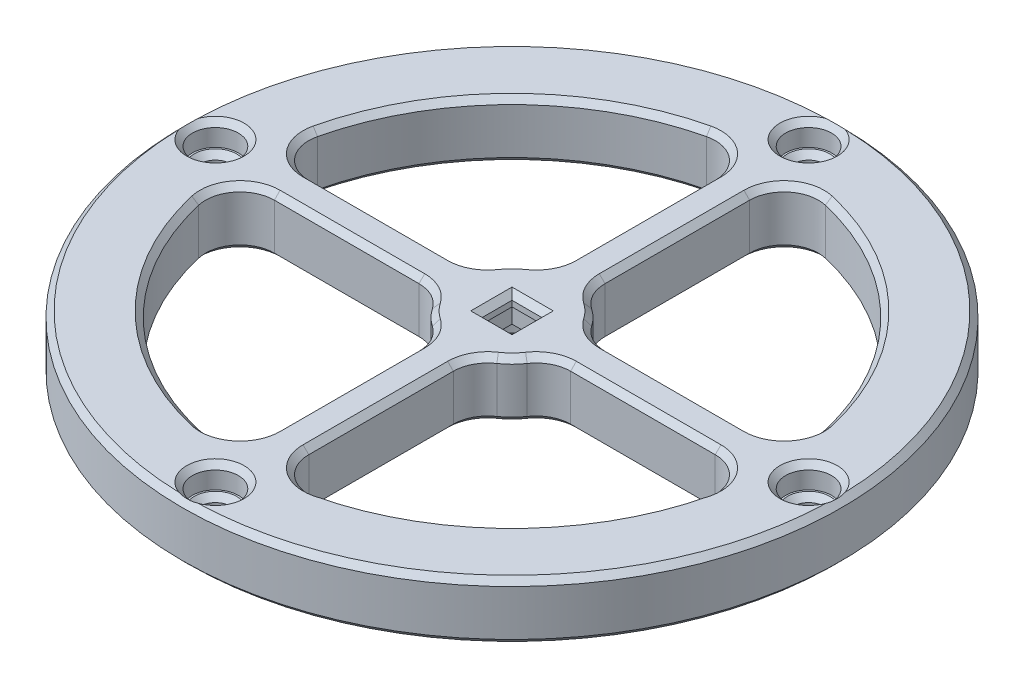
SolidWorks part; units mm, degrees
note: The reader was unsure of these and kept them because the rebuilt part matched: shared geometry of "Sketch1<4>", "Sketch1<5>".
ref_plane "Front Plane" through (0, 0, 0) normal (0, 0, 1) x (1, 0, 0)
ref_plane "Top Plane" through (0, 0, 0) normal (0, 1, 0) x (1, 0, 0)
ref_plane "Right Plane" through (0, 0, 0) normal (1, 0, 0) x (0, 0, -1)
sketch "Sketch1" plane through (0, 0, 0) normal (0, 1, 0) x (1, 0, 0)
  line L0 (0, 0) -> (0, 32.8612) construction
  line L1 (-1.651, -1.651) -> (1.651, -1.651)
  line L2 (-1.651, -1.651) -> (-1.651, 1.651)
  line L3 (-1.651, 1.651) -> (1.651, 1.651)
  line L4 (1.651, -1.651) -> (1.651, 1.651)
  line L5 (-1.651, -1.651) -> (1.651, 1.651) construction
  line L6 (-1.651, 1.651) -> (1.651, -1.651) construction
  line L7 (1.905, 0) -> (1.905, 32.8612)
  line L8 (-1.905, 0) -> (-1.905, 32.8612)
  line L9 (0, 1.905) -> (32.8612, 1.905)
  line L10 (0, -1.905) -> (32.8612, -1.905)
  line L11 (0, 0) -> (32.8612, 0) construction
  line L12 (1.905, 0) -> (1.905, -32.8612)
  line L13 (-1.905, 0) -> (-1.905, -32.8612)
  line L14 (0, 0) -> (0, -32.8612) construction
  line L15 (0, -1.905) -> (-32.8612, -1.905)
  line L16 (0, 1.905) -> (-32.8612, 1.905)
  line L17 (0, 0) -> (-32.8612, 0) construction
  line L18 (0, 0) -> (28.4587, 16.4306) construction
  line L19 (-3.175, -3.175) -> (3.175, -3.175)
  line L20 (-3.175, -3.175) -> (-3.175, 3.175)
  line L21 (-3.175, 3.175) -> (3.175, 3.175)
  line L22 (3.175, -3.175) -> (3.175, 3.175)
  line L23 (-3.175, -3.175) -> (3.175, 3.175) construction
  line L24 (-3.175, 3.175) -> (3.175, -3.175) construction
  line L25 (0, 0) -> (28.4587, -16.4306) construction
  line L26 (0, 0) -> (0, -32.8612) construction
  line L27 (0, 0) -> (-28.4587, -16.4306) construction
  line L28 (0, 0) -> (-28.4587, 16.4306) construction
  line L29 (0, 0) -> (23.2364, 23.2364) construction
  line L30 (0, 0) -> (32.8612, 0) construction
  line L31 (0, 0) -> (23.2364, -23.2364) construction
  line L32 (0, 0) -> (0, -32.8612) construction
  line L33 (0, 0) -> (-23.2364, -23.2364) construction
  line L34 (0, 0) -> (-32.8612, 0) construction
  line L35 (0, 0) -> (-23.2364, 23.2364) construction
  circle A0 centre (0, 0) radius 36.5125
  circle A1 centre (0, 0) radius 28.8925
  circle A2 centre (0, 32.8612) radius 1.7145
  circle A15 centre (0, 0) radius 6.35
  circle A16 centre (0, 32.8612) radius 2.54
  circle A17 centre (0, 0) radius 5.08
  circle A30 centre (28.4587, 16.4306) radius 1.7145
  circle A31 centre (28.4587, 16.4306) radius 2.54
  circle A32 centre (28.4587, -16.4306) radius 1.7145
  circle A33 centre (28.4587, -16.4306) radius 2.54
  circle A34 centre (0, -32.8612) radius 1.7145
  circle A35 centre (0, -32.8612) radius 2.54
  circle A36 centre (-28.4587, -16.4306) radius 1.7145
  circle A37 centre (-28.4587, -16.4306) radius 2.54
  circle A38 centre (-28.4587, 16.4306) radius 1.7145
  circle A39 centre (-28.4587, 16.4306) radius 2.54
  circle A40 centre (23.2364, 23.2364) radius 2.54
  circle A41 centre (23.2364, 23.2364) radius 1.7145
  circle A42 centre (32.8612, 0) radius 2.54
  circle A43 centre (32.8612, 0) radius 1.7145
  circle A44 centre (23.2364, -23.2364) radius 2.54
  circle A45 centre (23.2364, -23.2364) radius 1.7145
  circle A46 centre (0, -32.8612) radius 2.54
  circle A47 centre (0, -32.8612) radius 1.7145
  circle A48 centre (-23.2364, -23.2364) radius 2.54
  circle A49 centre (-23.2364, -23.2364) radius 1.7145
  circle A50 centre (-32.8612, 0) radius 2.54
  circle A51 centre (-32.8612, 0) radius 1.7145
  circle A52 centre (-23.2364, 23.2364) radius 2.54
  circle A53 centre (-23.2364, 23.2364) radius 1.7145
  point P24 (6.35, 6.35)
  point P27 (-0.7665, 0.3175)
  point P33 (0, 0)
  point P37 (0, 0)
  point P38 (-0.5499, 0.3175)
  point P59 (0, 0)
  point P71 (-0.5499, 0.3175)
  point P79 (0, 0)
  point P82 (0, 0)
  point P87 (-0.7665, 0.3175)
  dimension "D2" = 57.785
  dimension "D4" = 3.429
  dimension "D5" = 32.8612
  dimension "D8" = 12.7
  dimension "D12" = 5.08
  dimension "D13" = 10.16
  dimension "D6" = 73.025
  dimension "D3" = 3.302
  dimension "D16" = 6.35
  dimension "D9" = 1.905
  dimension "D10" = 1.905
  dimension "D11" = 4
  dimension "D7" = 6
  dimension "D14" = 8
extrude "Boss-Extrude1" add sketch "Sketch1" along normal blind 6.35
fillet "Fillet1" radius 3.81 8 edges at (-1.905, 3.175, -6.0575) (-6.0575, 3.175, -1.905) (1.905, 3.175, -6.0575) (6.0575, 3.175, -1.905) (6.0575, 3.175, 1.905) (1.905, 3.175, 6.0575) (-1.905, 3.175, 6.0575) (-6.0575, 3.175, 1.905)
fillet "Fillet2" radius 3.81 8 edges at (28.8296, 3.175, -1.905) (28.8296, 3.175, 1.905) (1.905, 3.175, 28.8296) (-1.905, 3.175, 28.8296) (-28.8296, 3.175, -1.905) (-28.8296, 3.175, 1.905) (1.905, 3.175, -28.8296) (-1.905, 3.175, -28.8296)
sketch "Sketch2" plane through (0, 6.35, 0) normal (0, 1, 0) x (1, 0, 0)
  circle A0 centre (0, 32.8612) radius 2.54 construction
  circle A4 centre (0, 32.8612) radius 2.54
  circle A8 centre (28.4587, 16.4306) radius 1.7145 construction
  circle A9 centre (23.2364, 23.2364) radius 1.7145 construction
  circle A10 centre (23.2364, 23.2364) radius 2.54 construction
  circle A11 centre (28.4587, 16.4306) radius 2.54 construction
  circle A12 centre (32.8612, 0) radius 1.7145 construction
  circle A13 centre (32.8612, 0) radius 2.54 construction
  circle A14 centre (28.4587, -16.4306) radius 1.7145 construction
  circle A15 centre (28.4587, -16.4306) radius 2.54 construction
  circle A16 centre (23.2364, -23.2364) radius 1.7145 construction
  circle A17 centre (23.2364, -23.2364) radius 2.54 construction
  circle A18 centre (0, -32.8612) radius 2.54 construction
  circle A19 centre (0, -32.8612) radius 1.7145 construction
  circle A20 centre (-23.2364, -23.2364) radius 1.7145 construction
  circle A21 centre (-23.2364, -23.2364) radius 2.54 construction
  circle A22 centre (-28.4587, -16.4306) radius 2.54 construction
  circle A23 centre (-28.4587, -16.4306) radius 1.7145 construction
  circle A24 centre (-32.8612, 0) radius 2.54 construction
  circle A25 centre (-32.8612, 0) radius 1.7145 construction
  circle A26 centre (-28.4587, 16.4306) radius 2.54 construction
  circle A27 centre (-28.4587, 16.4306) radius 1.7145 construction
  circle A28 centre (-23.2364, 23.2364) radius 2.54 construction
  circle A29 centre (-23.2364, 23.2364) radius 1.7145 construction
  circle A30 centre (28.4587, 16.4306) radius 1.7145
  circle A31 centre (23.2364, 23.2364) radius 1.7145
  circle A32 centre (23.2364, 23.2364) radius 2.54
  circle A33 centre (28.4587, 16.4306) radius 2.54
  circle A34 centre (32.8612, 0) radius 1.7145
  circle A35 centre (32.8612, 0) radius 2.54
  circle A36 centre (28.4587, -16.4306) radius 1.7145
  circle A37 centre (28.4587, -16.4306) radius 2.54
  circle A38 centre (23.2364, -23.2364) radius 1.7145
  circle A39 centre (23.2364, -23.2364) radius 2.54
  circle A40 centre (0, -32.8612) radius 2.54
  circle A41 centre (0, -32.8612) radius 1.7145
  circle A42 centre (-23.2364, -23.2364) radius 1.7145
  circle A43 centre (-23.2364, -23.2364) radius 2.54
  circle A44 centre (-28.4587, -16.4306) radius 2.54
  circle A45 centre (-28.4587, -16.4306) radius 1.7145
  circle A46 centre (-32.8612, 0) radius 2.54
  circle A47 centre (-32.8612, 0) radius 1.7145
  circle A48 centre (-28.4587, 16.4306) radius 2.54
  circle A49 centre (-28.4587, 16.4306) radius 1.7145
  circle A50 centre (-23.2364, 23.2364) radius 2.54
  circle A51 centre (-23.2364, 23.2364) radius 1.7145
extrude "Cut-Extrude4" cut sketch "Sketch2" against normal blind 2.54
extrude "Cut-Extrude2" cut sketch "Sketch1<4>" along normal blind 1.27 contours A17
sketch "Sketch1<4>" plane through (0, 0, 0) normal (0, 1, 0) x (1, 0, 0) same geometry as "Sketch1"
extrude "Cut-Extrude3" cut sketch "Sketch1<5>" along normal blind 5.08 contours L22 L21 L20 L19
sketch "Sketch1<5>" plane through (0, 0, 0) normal (0, 1, 0) x (1, 0, 0) same geometry as "Sketch1"
chamfer "Chamfer3" distance 0.635 angle 45 87 edges at (0, 6.35, 1.651) (1.651, 6.35, 0) (0, 6.35, -1.651) (-1.651, 6.35, 0) (27.408, 6.35, -3.3477) (27.408, 0, -3.3477) (20.4301, 0, -20.4301) (20.4301, 6.35, -20.4301) (3.3477, 6.35, -27.408) (3.3477, 0, -27.408) (1.905, 0, -16.4115) (1.905, 6.35, -16.4115) (2.3474, 6.35, -6.6183) (2.3474, 0, -6.6183) (4.4901, 0, -4.4901) (4.4901, 6.35, -4.4901) (6.6183, 6.35, -2.3474) (6.6183, 0, -2.3474) (16.4115, 6.35, -1.905) (16.4115, 0, -1.905) (0, 6.35, 36.5125) (0, 0, 36.5125) (-3.3477, 6.35, -27.408) (-3.3477, 0, -27.408) (-20.4301, 6.35, -20.4301) (-20.4301, 0, -20.4301) (-27.408, 6.35, -3.3477) (-27.408, 0, -3.3477) (-16.4115, 0, -1.905) (-16.4115, 6.35, -1.905) (-6.6183, 6.35, -2.3474) (-6.6183, 0, -2.3474) (-4.4901, 6.35, -4.4901) (-4.4901, 0, -4.4901) (-2.3474, 6.35, -6.6183) (-2.3474, 0, -6.6183) (-1.905, 6.35, -16.4115) (-1.905, 0, -16.4115) (-27.408, 6.35, 3.3477) (-27.408, 0, 3.3477) (-20.4301, 6.35, 20.4301) (-20.4301, 0, 20.4301) (-3.3477, 6.35, 27.408) (-3.3477, 0, 27.408) (-1.905, 0, 16.4115) (-1.905, 6.35, 16.4115) (-2.3474, 6.35, 6.6183) (-2.3474, 0, 6.6183) (-4.4901, 0, 4.4901) (-4.4901, 6.35, 4.4901) (-6.6183, 6.35, 2.3474) (-6.6183, 0, 2.3474) (-16.4115, 6.35, 1.905) (-16.4115, 0, 1.905) (3.3477, 6.35, 27.408) (3.3477, 0, 27.408) (20.4301, 6.35, 20.4301) (20.4301, 0, 20.4301) (27.408, 6.35, 3.3477) (27.408, 0, 3.3477) (16.4115, 0, 1.905) (16.4115, 6.35, 1.905) (6.6183, 6.35, 2.3474) (6.6183, 0, 2.3474) (4.4901, 0, 4.4901) (4.4901, 6.35, 4.4901) (2.3474, 6.35, 6.6183) (2.3474, 0, 6.6183) (1.905, 6.35, 16.4115) (1.905, 0, 16.4115) (0, 6.35, -30.3212) (0, 0, -31.1467) (0, 3.81, -31.1467) (0, 0, 5.08) (-32.8612, 0, 1.7145) (-32.8612, 3.81, 1.7145) (32.8612, 0, 1.7145) (32.8612, 3.81, 1.7145) (0, 0, 34.5757) (0, 3.81, 34.5757) (0, 6.35, 35.4012) (-32.8612, 6.35, 2.54) (32.8612, 6.35, 2.54) (0, 1.27, -3.175) (3.175, 1.27, 0) (-3.175, 1.27, 0) (0, 1.27, 3.175)
